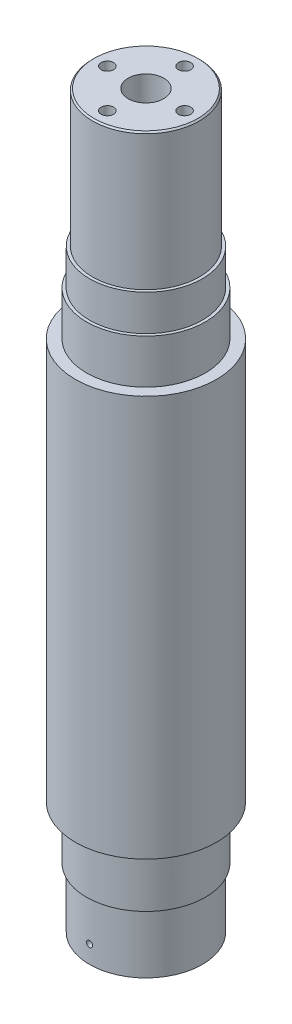
SolidWorks part; units mm, degrees
material "Stainless Steel (ferritic)"
ref_plane "Front" through (0, 0, 0) normal (0, 0, 1) x (1, 0, 0)
ref_plane "Top" through (0, 0, 0) normal (0, 1, 0) x (1, 0, 0)
ref_plane "Right" through (0, 0, 0) normal (1, 0, 0) x (0, 0, -1)
sketch "Sketch1" plane through (0, 0, 0) normal (0, 1, 0) x (1, 0, 0)
  circle A0 centre (0, 0) radius 25
  dimension "D1" = 50
extrude "Boss-Extrude1" add sketch "Sketch1" along normal blind 95 and the other way blind 105
sketch "Sketch2" plane through (0, 95, 0) normal (0, 1, 0) x (1, 0, 0)
  circle A0 centre (0, 0) radius 18
  dimension "D1" = 36
extrude "Boss-Extrude2" add sketch "Sketch2" along normal blind 46
ref_plane "Plane1" through (0, 0, -15) normal (0, 0, 1) x (1, 0, 0)
sketch "Sketch8" plane through (0, 0, -15) normal (0, 0, 1) x (1, 0, 0)
  line L0 (0, 122) -> (0, 103) construction
  line L1 (3, 122) -> (3, 103)
  line L2 (-3, 122) -> (-3, 103)
  line L4 (25, 95) -> (-25, 95) construction
  arc A0 (3, 122) -> (-3, 122) centre (0, 122) ccw
  arc A1 (-3, 103) -> (3, 103) centre (0, 103) ccw
  point P2 (0, 112.5)
  dimension "D2" = 3
  dimension "D1" = 17.5
  dimension "D3" = 9.5
extrude "Cut-Extrude1" cut sketch "Sketch8" against normal blind 10
chamfer "Chamfer1" distance 0.5 angle 45 1 edges at (0, 141, 18)
sketch "Sketch9" plane through (0, -105, 0) normal (0, -1, 0) x (1, 0, 0)
  circle A0 centre (0, 0) radius 10
  dimension "D1" = 20
extrude "Cut-Extrude2" cut sketch "Sketch9" against normal blind 30 draft 8
sketch "Sketch10" plane through (0, -105, 0) normal (0, -1, 0) x (1, 0, 0)
  circle A0 centre (0, 0) radius 6.5
  dimension "D1" = 13
extrude "Cut-Extrude3" cut sketch "Sketch10" against normal blind 50
sketch "Sketch11" plane through (0, 141, 0) normal (0, 1, 0) x (1, 0, 0)
  circle A0 centre (0, 0) radius 6
  dimension "D1" = 12
extrude "Cut-Extrude4" cut sketch "Sketch11" against normal through all
hole_wizard "M5x0.8 Tapped Hole1" positions "Sketch13" profile "Sketch15" tap size "M5x0.8" standard "ANSI Metric"
sketch "Sketch13" plane through (0, 141, 0) normal (0, 1, 0) x (1, 0, 0)
  point P0 (0, 13)
  dimension "D1" = 13
sketch "Sketch15" plane through (0, 141, -13) normal (1, 0, 0) x (0, 0, 1)
  line L0 (0, 0) -> (0, 12)
  line L1 (0, 12) -> (2.1, 10.7382)
  line L2 (2.1, 10.7382) -> (2.1, 0)
  line L5 (2.1, 0) -> (0, 0)
  line L10 (0, 12) -> (-2.1, 10.7382) construction
  line L11 (0, -6.35) -> (0, 107.95) construction
  dimension "Tap Drill Dia." = 4.2
  dimension "Tap Drill Depth" = 12
  dimension "Drill Angle" = 118
cosmetic thread "Hole Thread1" parameters "D1"=10, "D2"=5
pattern_circular "CirPattern1" count 4 over 360 about axis through (0, -105, 0) along (0, 1, 0) of "M5x0.8 Tapped Hole1" reverse direction yes
cosmetic thread "Hole Thread2" parameters "D1"=10, "D2"=5
cosmetic thread "Hole Thread3" parameters "D1"=10, "D2"=5
cosmetic thread "Hole Thread4" parameters "D1"=10, "D2"=5
hole_wizard "M2.5x0.45 Tapped Hole1" positions "Sketch19" profile "Sketch20" tap size "M2.5x0.45" standard "ANSI Metric"
sketch "Sketch19" plane through (0, -105, 0) normal (0, -1, 0) x (-1, 0, 0)
  point P0 (-12.2, 0)
  dimension "D1" = 12.2
sketch "Sketch20" plane through (12.2, -105, 0) normal (1, 0, 0) x (0, 0, -1)
  line L0 (0, 0) -> (0, 9.35)
  line L1 (0, 9.35) -> (1.025, 8.7341)
  line L2 (1.025, 8.7341) -> (1.025, 0)
  line L5 (1.025, 0) -> (0, 0)
  line L10 (0, 9.35) -> (-1.025, 8.7341) construction
  line L11 (0, -6.35) -> (0, 107.95) construction
  dimension "Tap Drill Dia." = 2.05
  dimension "Tap Drill Depth" = 9.35
  dimension "Drill Angle" = 118
cosmetic thread "Hole Thread7" parameters "D1"=8, "D2"=2.5
mirror "Mirror2" about plane through (0, 0, 0) normal (1, 0, 0) of "M2.5x0.45 Tapped Hole1"
cosmetic thread "Hole Thread8" parameters "D1"=8, "D2"=2.5
sketch "Sketch21" plane through (0, -1, 0) normal (0, 1, 0) x (1, 0, 0)
  circle A0 centre (0, 0) radius 20
  circle A1 centre (0, 0) radius 25
  dimension "D1" = 40
  dimension "D2" = 50
extrude "Cut-Extrude6" cut sketch "Sketch21" along normal blind 27 from offset 69
extrude "Cut-Extrude7" cut sketch "Sketch21<2>" against normal blind 39 from offset 66 offset against normal yes
sketch "Sketch21<2>" plane through (0, -1, 0) normal (0, 1, 0) x (1, 0, 0) same geometry as "Sketch21"
sketch "Sketch23" plane through (0, 95, 0) normal (0, 1, 0) x (1, 0, 0)
  circle A0 centre (0, 0) radius 25
  circle A1 centre (0, 0) radius 23.75
  dimension "D1" = 47.5
  dimension "D2" = 50
extrude "Cut-Extrude8" cut sketch "Sketch23" against normal blind 135 from offset 27 offset against normal yes
sketch "Sketch24" plane through (0, -105, 0) normal (0, -1, 0) x (1, 0, 0)
  circle A0 centre (0, 0) radius 19
  circle A1 centre (0, 0) radius 20
  dimension "D1" = 38
  dimension "D2" = 40
extrude "Cut-Extrude9" cut sketch "Sketch24" against normal blind 20.1
hole_wizard "M2.5x0.45 Tapped Hole2" positions "3DSketch1" profile "Sketch22" tap size "M2.5x0.45" standard "ANSI Metric"
sketch3d "3DSketch1"
  point P0 (0, -99, -19)
  point P2 (0, -99, 19)
sketch "Sketch22" plane through (0, -99, -19) normal (1, 0, 0) x (0, 1, 0)
  line L0 (0, 0) -> (0, 5.6159)
  line L1 (0, 5.6159) -> (1.025, 5)
  line L2 (1.025, 5) -> (1.025, 0)
  line L5 (1.025, 0) -> (0, 0)
  line L10 (0, 5.6159) -> (-1.025, 5) construction
  line L11 (0, -6.35) -> (0, 107.95) construction
  dimension "Tap Drill Dia." = 2.05
  dimension "Tap Drill Depth" = 5
  dimension "Drill Angle" = 118
cosmetic thread "Hole Thread9" parameters "D1"=5, "D2"=2.5
cosmetic thread "Hole Thread10" parameters "D1"=5, "D2"=2.5
sketch "Sketch25" plane through (0, 95, 0) normal (0, 1, 0) x (1, 0, 0)
  circle A0 centre (0, 0) radius 19
  circle A1 centre (0, 0) radius 20
  dimension "D1" = 38
  dimension "D2" = 40
extrude "Cut-Extrude10" cut sketch "Sketch25" against normal blind 12.1
